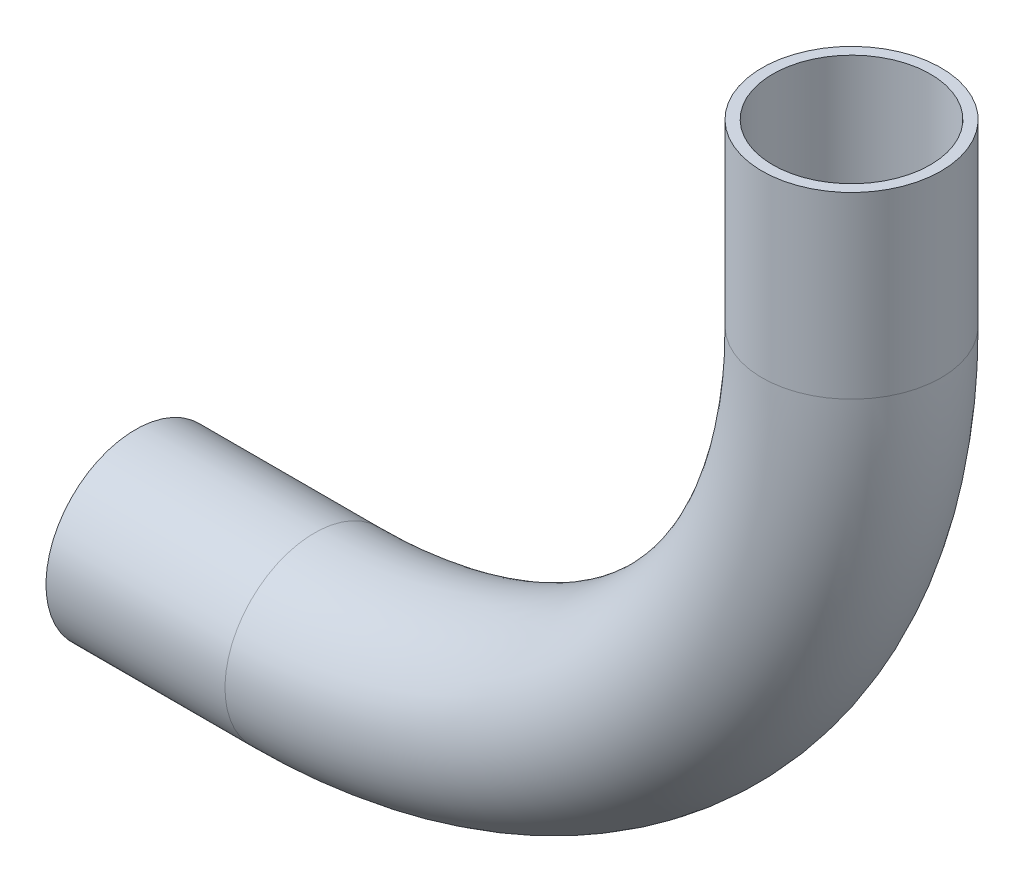
SolidWorks part; units mm, degrees
ref_plane "Front Plane" through (0, 0, 0) normal (0, 0, 1) x (1, 0, 0)
ref_plane "Top Plane" through (0, 0, 0) normal (0, 1, 0) x (1, 0, 0)
ref_plane "Right Plane" through (0, 0, 0) normal (1, 0, 0) x (0, 0, -1)
sketch "Sketch1" plane through (0, 0, 0) normal (0, 0, 1) x (1, 0, 0)
  line L0 (51.1289, 36.3501) -> (51.1289, 23.6501)
  line L1 (13.0289, -14.4499) -> (0.3289, -14.4499)
  arc A0 (51.1289, 23.6501) -> (13.0289, -14.4499) centre (13.0289, 23.6501) cw
  point P4 (14.9978, 41.018)
  dimension "D1" = 38.1
  dimension "D2" = 12.7
  dimension "D3" = 12.7
  dimension "D4" = 90
ref_plane "Plane1" through (51.1289, 36.3501, 0) normal (0, -1, 0) x (0, 0, -1)
sketch "Sketch2" plane through (51.1289, 36.3501, 0) normal (0, -1, 0) x (0, 0, -1)
  line L0 (0, 0) -> (0, -38.1) construction
  circle A0 centre (0, 0) radius 6.35
  circle A1 centre (0, 0) radius 5.588
  dimension "D1" = 11.176
  dimension "D2" = 12.7
sweep "Sweep1" add profiles "Sketch2" path "Sketch1"
